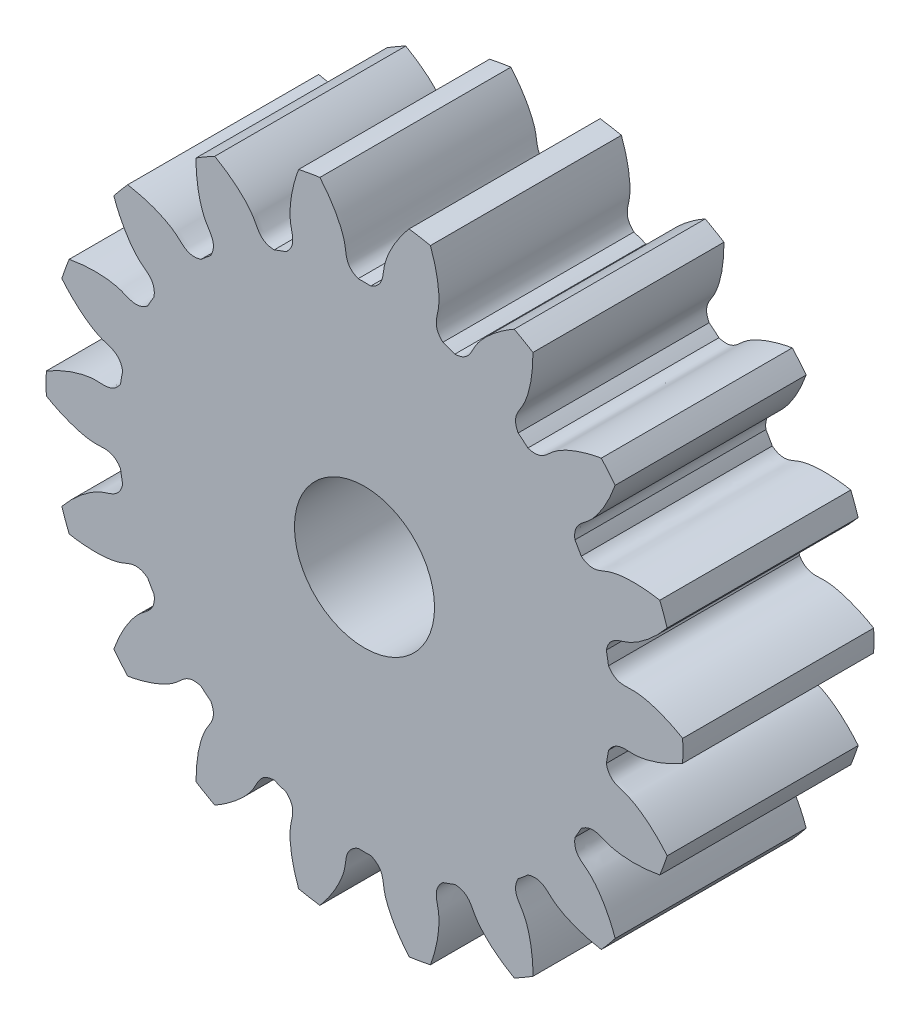
SolidWorks part; units mm, degrees
ref_plane "前视基准面" through (0, 0, 0) normal (0, 0, 1) x (1, 0, 0)
ref_plane "上视基准面" through (0, 0, 0) normal (0, 1, 0) x (1, 0, 0)
ref_plane "右视基准面" through (0, 0, 0) normal (1, 0, 0) x (0, 0, -1)
other "Configuration Table"
sketch "草图1" plane through (0, 0, 0) normal (0, 0, 1) x (1, 0, 0)
  circle A0 centre (0, 0) radius 5
extrude "凸台-拉伸1" add sketch "草图1" along normal blind 3
ref_axis "基准轴1" through (0, 0, 3) along (0, 0, -1)
sketch "草图2" plane through (0, 0, 0) normal (0, 0, 1) x (1, 0, 0)
  line L0 (0, 0) -> (0, 5) construction
  circle A0 centre (0, 0) radius 5 construction
  arc A1 (0.0997, 3.8737) -> (-0.0997, 3.8737) centre (0, 0) ccw
  arc A2 (1.5493, 5.6533) -> (-1.5493, 5.6533) centre (0, 0) ccw
  spline S0 degree 3 poles (0.0997, 3.8737) (0.3076, 3.9593) (0.2814, 4.1193) (0.3159, 4.2713) (0.3194, 4.2853) (0.3236, 4.3008) (0.3285, 4.3178) (0.3343, 4.3364) (0.341, 4.3564) (0.3487, 4.378) (0.3574, 4.4009) (0.3672, 4.4252) (0.3781, 4.4509) (0.3903, 4.4779) (0.4037, 4.5062) (0.4184, 4.5357) (0.4345, 4.5664) (0.452, 4.5982) (0.471, 4.6312) (0.4916, 4.6653) (0.5137, 4.7003) (0.5374, 4.7363) (0.5628, 4.7733) (0.5899, 4.8111) (0.6188, 4.8496) (0.6495, 4.889) (0.6821, 4.929) (0.7165, 4.9697) (0.7529, 5.0109) (0.7912, 5.0527) (0.8315, 5.0949) (0.8738, 5.1374) (0.9182, 5.1803) (0.9647, 5.2235) (1.0133, 5.2668) (1.0641, 5.3103) (1.117, 5.3538) (1.1721, 5.3973) (1.2294, 5.4407) (1.289, 5.4839) (1.3507, 5.527) (1.437, 5.5845) (1.5038, 5.6262) (1.5493, 5.6533) knots 0 0 0 0 0.187592 0.192996 0.199121 0.205966 0.213531 0.221818 0.230824 0.240552 0.250999 0.262168 0.274057 0.286666 0.299996 0.314047 0.328818 0.344309 0.360521 0.377454 0.395107 0.413481 0.432575 0.45239 0.472926 0.494181 0.516158 0.538855 0.562272 0.58641 0.611269 0.636848 0.663148 0.690168 0.717909 0.74637 0.775552 0.805454 0.836077 0.867421 0.899485 0.932269 1 1 1 1
  spline S1 degree 3 poles (-0.0997, 3.8737) (-0.3076, 3.9593) (-0.2814, 4.1193) (-0.3159, 4.2713) (-0.3194, 4.2853) (-0.3236, 4.3008) (-0.3285, 4.3178) (-0.3343, 4.3364) (-0.341, 4.3564) (-0.3487, 4.378) (-0.3574, 4.4009) (-0.3672, 4.4252) (-0.3781, 4.4509) (-0.3903, 4.4779) (-0.4037, 4.5062) (-0.4184, 4.5357) (-0.4345, 4.5664) (-0.452, 4.5982) (-0.471, 4.6312) (-0.4916, 4.6653) (-0.5137, 4.7003) (-0.5374, 4.7363) (-0.5628, 4.7733) (-0.5899, 4.8111) (-0.6188, 4.8496) (-0.6495, 4.889) (-0.6821, 4.929) (-0.7165, 4.9697) (-0.7529, 5.0109) (-0.7912, 5.0527) (-0.8315, 5.0949) (-0.8738, 5.1374) (-0.9182, 5.1803) (-0.9647, 5.2235) (-1.0133, 5.2668) (-1.0641, 5.3103) (-1.117, 5.3538) (-1.1721, 5.3973) (-1.2294, 5.4407) (-1.289, 5.4839) (-1.3507, 5.527) (-1.437, 5.5845) (-1.5038, 5.6262) (-1.5493, 5.6533) knots 0 0 0 0 0.187592 0.192996 0.199121 0.205966 0.213531 0.221818 0.230824 0.240552 0.250999 0.262168 0.274057 0.286666 0.299996 0.314047 0.328818 0.344309 0.360521 0.377454 0.395107 0.413481 0.432575 0.45239 0.472926 0.494181 0.516158 0.538855 0.562272 0.58641 0.611269 0.636848 0.663148 0.690168 0.717909 0.74637 0.775552 0.805454 0.836077 0.867421 0.899485 0.932269 1 1 1 1
extrude "切除-拉伸1" cut sketch "草图2" along normal through all
pattern_circular "阵列(圆周)1" count 18 every 20 about axis through (0, 0, 3) along (0, 0, -1) of "切除-拉伸1"
sketch "草图3" plane through (0, 0, 0) normal (0, 0, 1) x (1, 0, 0)
  circle A0 centre (0, 0) radius 4.5 construction
  dimension "Dn" = 9
sketch "草图4" plane through (0, 0, 0) normal (0, 0, -1) x (-1, 0, 0)
  circle A0 centre (0, 0) radius 1.1
  dimension "D1" = 2.2
extrude "切除-拉伸2" cut sketch "草图4" against normal up to next
